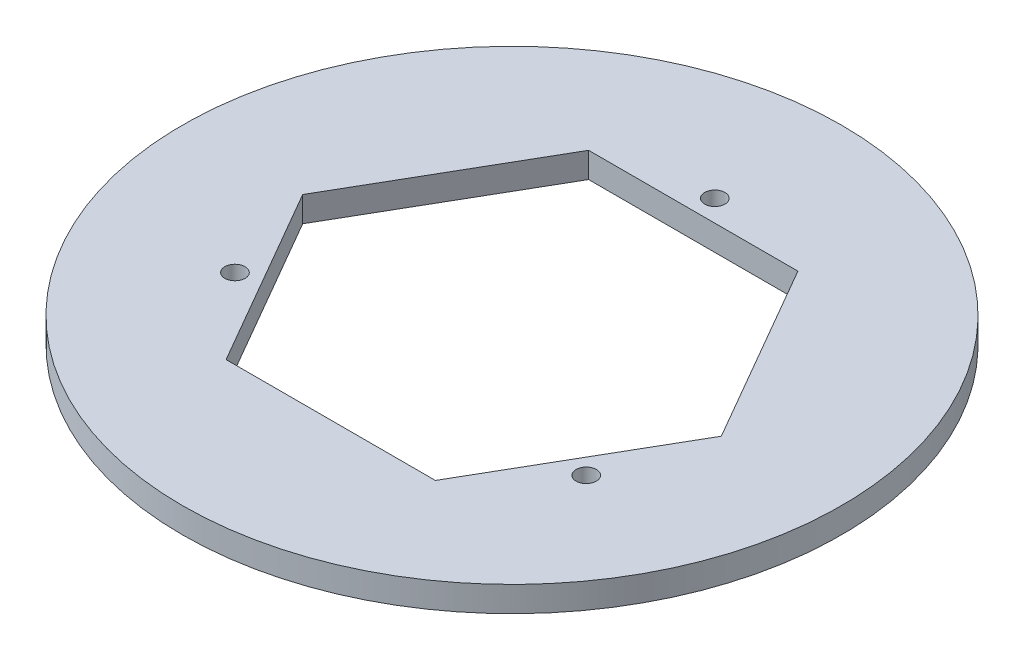
SolidWorks part; units mm, degrees
ref_plane "Ebene vorne" through (0, 0, 0) normal (0, 0, 1) x (1, 0, 0)
ref_plane "Ebene oben" through (0, 0, 0) normal (0, 1, 0) x (1, 0, 0)
ref_plane "Ebene rechts" through (0, 0, 0) normal (1, 0, 0) x (0, 0, -1)
sketch "Skizze1" plane through (0, 0, 0) normal (0, 1, 0) x (1, 0, 0)
  line L0 (0, 0) -> (41.2805, 0) construction
  line L1 (41.2805, 0) -> (20.6403, 35.75)
  line L2 (20.6403, 35.75) -> (-20.6403, 35.75)
  line L3 (-20.6403, 35.75) -> (-41.2805, 0)
  line L4 (-41.2805, 0) -> (-20.6403, -35.75)
  line L5 (-20.6403, -35.75) -> (20.6403, -35.75)
  line L6 (20.6403, -35.75) -> (41.2805, 0)
  line L7 (0, 0) -> (0, 40) construction
  circle A0 centre (0, 0) radius 35.75 construction
  circle A1 centre (0, 0) radius 65
  circle A2 centre (0, 40) radius 2
  circle A3 centre (34.641, -20) radius 2
  circle A4 centre (-34.641, -20) radius 2
  point P13 (-47.4293, -20.6184)
  point P18 (0, 0)
  dimension "D1" = 71.5
  dimension "D2" = 130
  dimension "D3" = 4
  dimension "D4" = 40
  dimension "D5" = 3
extrude "Aufsatz-Linear austragen1" add sketch "Skizze1" along normal blind 5
